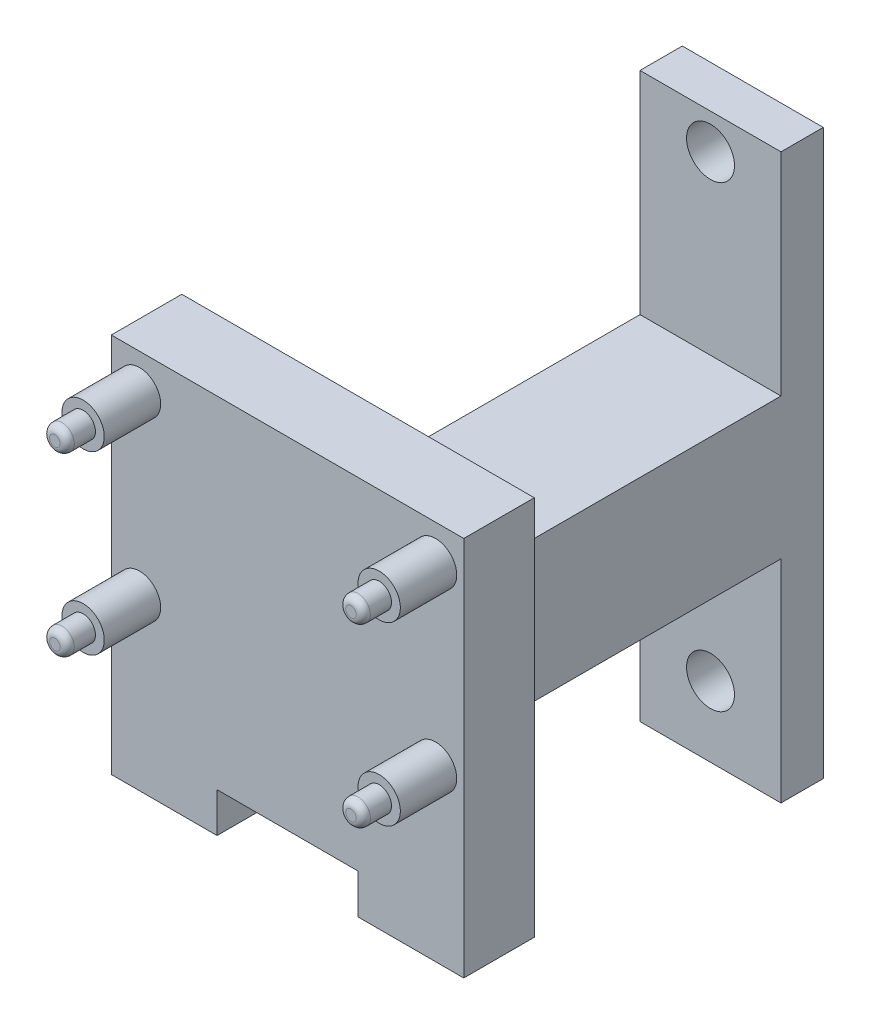
SolidWorks part; units mm, degrees
ref_plane "Front Plane" through (0, 0, 0) normal (0, 0, 1) x (1, 0, 0)
ref_plane "Top Plane" through (0, 0, 0) normal (0, 1, 0) x (1, 0, 0)
ref_plane "Right Plane" through (0, 0, 0) normal (1, 0, 0) x (0, 0, -1)
sketch "Sketch1" plane through (0, 0, 0) normal (0, 0, 1) x (1, 0, 0)
  line L1 (0, 0) -> (10, 0)
  line L2 (0, 0) -> (0, 40)
  line L3 (0, 40) -> (10, 40)
  line L4 (10, 0) -> (10, 40)
  dimension "D1" = 40
  dimension "D2" = 10
extrude "Boss-Extrude1" add sketch "Sketch1" along normal blind 3
sketch "Sketch2" plane through (0, 0, 3) normal (0, 0, 1) x (1, 0, 0)
  line L2 (10, 0) -> (10, 40) construction
  line L3 (10, 40) -> (0, 40) construction
  line L6 (0, 0) -> (10, 0) construction
  circle A3 centre (5, 37.5) radius 1.7
  circle A4 centre (5, 5) radius 1.7
  dimension "D1" = 2.5
  dimension "D2" = 5
  dimension "D5" = 3.4
  dimension "D6" = 3.4
  dimension "D3" = 5
  dimension "D4" = 5
extrude "Cut-Extrude1" cut sketch "Sketch2" against normal blind 7
sketch "Sketch3" plane through (0, 0, 3) normal (0, 0, 1) x (1, 0, 0)
  line L7 (0, 25) -> (10, 25)
  line L8 (0, 25) -> (0, 15)
  line L9 (0, 15) -> (10, 15)
  line L10 (10, 25) -> (10, 15)
  line L11 (10, 0) -> (10, 40) construction
  line L12 (0, 40) -> (0, 0) construction
  point P11 (0, 20)
  point P12 (0, 20)
  dimension "D1" = 10
extrude "Boss-Extrude2" add sketch "Sketch3" along normal blind 25
sketch "Sketch7" plane through (0, 0, 28) normal (0, 0, 1) x (1, 0, 0)
  line L1 (-7.5, 8) -> (17.5, 8)
  line L2 (-7.5, 8) -> (-7.5, 32)
  line L4 (17.5, 8) -> (17.5, 32)
  line L5 (10, 0) -> (10, 40) construction
  line L6 (-7.5, 32) -> (-7.5, 35)
  line L7 (-7.5, 35) -> (17.5, 35)
  line L8 (17.5, 35) -> (17.5, 32)
  circle A0 centre (-5.5, 20) radius 1
  circle A1 centre (15.5, 20) radius 1
  circle A2 centre (-5.5, 32.5) radius 1
  circle A3 centre (15.5, 32.5) radius 1
  point P19 (10, 20)
  point P20 (17.5, 20)
  dimension "D3" = 2
  dimension "D7" = 24.5
  dimension "D1" = 24
  dimension "D2" = 25
  dimension "D4" = 12
  dimension "D5" = 2
  dimension "D6" = 2
  dimension "D8" = 3
extrude "Boss-Extrude3" add sketch "Sketch7" along normal blind 5
sketch "Sketch9" plane through (0, 0, 28) normal (0, 0, -1) x (-1, 0, 0)
  circle A0 centre (5.5, 32.5) radius 1.5
  circle A1 centre (-15.5, 32.5) radius 1.5
  circle A2 centre (-15.5, 20) radius 1.5
  circle A3 centre (5.5, 20) radius 1.5
  dimension "D1" = 3
extrude "Boss-Extrude4" add sketch "Sketch9" against normal blind 9
sketch "Sketch10" plane through (0, 0, 37) normal (0, 0, 1) x (1, 0, 0)
  circle A0 centre (-5.5, 32.5) radius 0.875
  circle A1 centre (15.5, 32.5) radius 0.875
  circle A2 centre (15.5, 20) radius 0.875
  circle A3 centre (-5.5, 20) radius 0.875
  dimension "D1" = 1.75
extrude "Boss-Extrude5" add sketch "Sketch10" along normal blind 2
fillet "Fillet1" radius 0.5 4 edges at (16.375, 32.5, 39) (16.375, 20, 39) (-4.625, 20, 39) (-4.625, 32.5, 39)
chamfer "Chamfer1" distance 7.5 angle 45 2 edges at (10, 20, 28) (0, 20, 28)
chamfer "Chamfer2" distance 7 angle 45 2 edges at (5, 15, 28) (5, 25, 28)
sketch "Sketch11" plane through (0, 0, 33) normal (0, 0, 1) x (1, 0, 0)
  line L1 (0, 10.8196) -> (10, 10.8196)
  line L2 (0, 10.8196) -> (0, 8)
  line L3 (0, 8) -> (10, 8)
  line L4 (10, 10.8196) -> (10, 8)
  line L8 (-7.5, 8) -> (17.5, 8) construction
  point P6 (10, 32)
  point P9 (10, 8)
  point P10 (0, 8)
  point P14 (0, 8)
extrude "Cut-Extrude2" cut sketch "Sketch11" against normal blind 10
